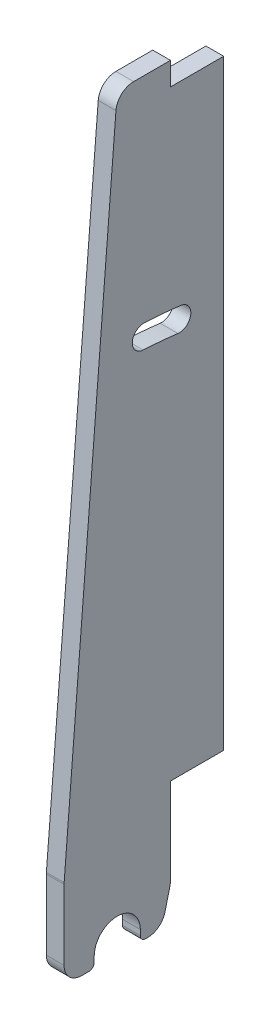
SolidWorks part; units mm, degrees
ref_plane "Front Plane" through (0, 0, 0) normal (0, 0, 1) x (1, 0, 0)
ref_plane "Top Plane" through (0, 0, 0) normal (0, 1, 0) x (1, 0, 0)
ref_plane "Right Plane" through (0, 0, 0) normal (1, 0, 0) x (0, 0, -1)
sketch "Sketch1" plane through (0, 0, 0) normal (1, 0, 0) x (0, 0, -1)
  line L0 (30, 0) -> (0, 0)
  line L1 (0, 0) -> (0, -50)
  line L2 (0, -50) -> (-5, -70)
  line L3 (-5, -70) -> (-17, -70)
  line L4 (-60, -70) -> (-60, -20)
  line L5 (-30, 352) -> (30, 352)
  line L7 (30, 352) -> (30, 0)
  line L8 (-43, -70) -> (-60, -70)
  line L9 (-60, -20) -> (-30, 352)
  line L10 (-43, -64) -> (-43, -70)
  line L11 (-17, -64) -> (-17, -70)
  arc A0 (-43, -64) -> (-17, -64) centre (-30, -64) cw
  dimension "D1" = 64
  dimension "D2" = 13
  dimension "D3" = 30
  dimension "D4" = 60
  dimension "D5" = 25
  dimension "D6" = 50
  dimension "D7" = 30
  dimension "D8" = 352
  dimension "D9" = 60
  dimension "D12" = 50
  dimension "D13" = 70
extrude "Boss-Extrude1" add sketch "Sketch1" along normal mid plane 10
fillet "Fillet1" radius 10 5 edges at (0, -70, 60) (0, -70, 5) (0, -50, 0) (0, -20, 60) (0, 352, 30)
fillet "Fillet2" radius 3 2 edges at (0, -70, 17) (0, -70, 43)
sketch "Sketch2" plane through (5, 0, 0) normal (1, 0, 0) x (0, 0, -1)
  line L8 (30, 0) -> (30, 352) construction
  line L9 (30, 339) -> (0, 339)
  line L10 (30, 339) -> (30, 352)
  line L11 (30, 352) -> (0, 352)
  line L12 (0, 339) -> (0, 352)
  line L13 (30, 352) -> (-20.774, 352) construction
  line L14 (0, 0) -> (0, 339) construction
  dimension "D1" = 13
extrude "Cut-Extrude1" cut sketch "Sketch2" against normal through all
sketch "Sketch3" plane through (5, 0, 0) normal (1, 0, 0) x (0, 0, -1)
  line L0 (30, 0) -> (30, 339) construction
  line L1 (-50, -70) -> (-46, -70) construction
  circle A0 centre (-5, 224) radius 6.5
  dimension "D1" = 35
  dimension "D3" = 13
  dimension "D2" = 294
extrude "Cut-Extrude2" cut sketch "Sketch3" against normal through all
sketch "Sketch4" plane through (5, 0, 0) normal (1, 0, 0) x (0, 0, -1)
  arc A0 (-15.0151, 224.6944) -> (4.9849, 222.9583) centre (-30, -64) cw construction
  arc A1 (5.7716, 229.4105) -> (-14.6781, 231.1857) centre (-30, -64) ccw
  arc A2 (4.1983, 216.5061) -> (-15.352, 218.2031) centre (-30, -64) ccw
  arc A3 (4.1983, 216.5061) -> (5.7716, 229.4105) centre (4.9849, 222.9583) ccw
  arc A4 (-14.6781, 231.1857) -> (-15.352, 218.2031) centre (-15.0151, 224.6944) ccw
  point P4 (-5, 224)
  dimension "D1" = 6.5
  dimension "D2" = 20
extrude "Cut-Extrude3" cut sketch "Sketch4" against normal through all
